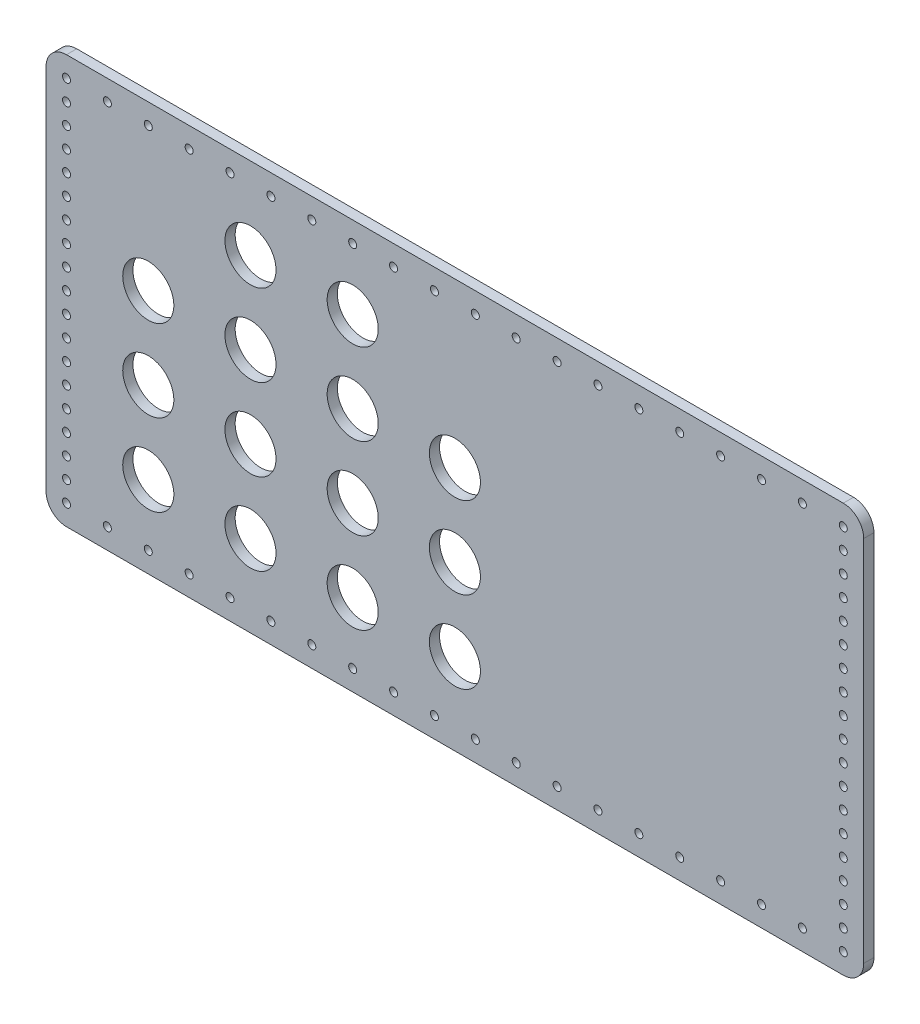
SolidWorks part; units mm, degrees
material "PC High Viscosity"
ref_plane "Front Plane" through (0, 0, 0) normal (0, 0, 1) x (1, 0, 0)
ref_plane "Top Plane" through (0, 0, 0) normal (0, 1, 0) x (1, 0, 0)
ref_plane "Right Plane" through (0, 0, 0) normal (1, 0, 0) x (0, 0, -1)
sketch "Sketch1" plane through (0, 0, 0) normal (0, 0, 1) x (1, 0, 0)
  line L1 (0, 0) -> (508, 0)
  line L2 (0, 0) -> (0, 254)
  line L3 (0, 254) -> (508, 254)
  line L4 (508, 0) -> (508, 254)
  dimension "D1" = 508
  dimension "D2" = 254
extrude "Boss-Extrude1" add sketch "Sketch1" along normal blind 6.35
sketch "Sketch3" plane through (0, 0, 0) normal (0, 0, -1) x (-1, 0, 0)
  line L14 (0, 0) -> (-508, 0) construction
  line L15 (0, 254) -> (0, 0) construction
  line L16 (-127, 152.4) -> (-190.5, 152.4) construction
  line L17 (-127, 152.4) -> (-127, 203.2) construction
  circle A5 centre (-127, 152.4) radius 15.875
  circle A6 centre (-63.5, 152.4) radius 15.875
  circle A7 centre (-190.5, 152.4) radius 15.875
  circle A8 centre (-127, 101.6) radius 15.875
  circle A9 centre (-63.5, 101.6) radius 15.875
  circle A10 centre (-190.5, 101.6) radius 15.875
  circle A11 centre (-127, 50.8) radius 15.875
  circle A12 centre (-63.5, 50.8) radius 15.875
  circle A13 centre (-190.5, 50.8) radius 15.875
  circle A15 centre (-190.5, 152.4) radius 15.875
  circle A16 centre (-254, 152.4) radius 15.875
  circle A17 centre (-254, 101.6) radius 15.875
  circle A18 centre (-254, 50.8) radius 15.875
  circle A19 centre (-190.5, 203.2) radius 15.875 [skipped]
  circle A20 centre (-254, 203.2) radius 15.875 [skipped]
  circle A21 centre (-254, 152.4) radius 15.875 [skipped]
  circle A22 centre (-254, 101.6) radius 15.875 [skipped]
  circle A23 centre (-127, 203.2) radius 15.875
  circle A24 centre (-190.5, 203.2) radius 15.875
  circle A25 centre (-190.5, 152.4) radius 15.875
  circle A26 centre (-190.5, 101.6) radius 15.875
  dimension "D2" = 31.75
  dimension "D3" = 50.8
  dimension "D4" = 50.8
  dimension "D5" = 50.8
  dimension "D6" = 63.5
  dimension "D7" = 63.5
  dimension "D8" = 2
  dimension "D9" = 2
  dimension "D10" = 63.5
  dimension "D11" = 50.8
  dimension "D12" = 63.5
extrude "Cut-Extrude2" cut sketch "Sketch3" against normal through all contours A18 | A17 | A16 | A24 | A7 | A10 | A8 | A5 | A23 | A6 | A9 | A12 | A11 | A13 region at (127, 152.4, 0) region at (63.5, 152.4, 0) region at (190.5, 152.4, 0) region at (127, 101.6, 0) region at (63.5, 101.6, 0) region at (190.5, 101.6, 0) region at (127, 50.8, 0) region at (63.5, 50.8, 0) region at (190.5, 50.8, 0) region at (254, 152.4, 0) region at (254, 101.6, 0) region at (254, 50.8, 0) region at (190.5, 203.2, 0) region at (127, 203.2, 0)
sketch "Sketch4" plane through (0, 0, 0) normal (0, 0, -1) x (-1, 0, 0)
  line L0 (0, 254) -> (0, 0) construction
  line L1 (-508, 254) -> (0, 254) construction
  line L2 (-12.7, 241.3) -> (-38.1, 241.3) construction
  line L3 (-495.3, 241.3) -> (-495.3, 228.6) construction
  line L4 (-495.3, 12.7) -> (-469.9, 12.7) construction
  circle A0 centre (-12.7, 241.3) radius 2.4892
  circle A1 centre (-38.1, 241.3) radius 2.4892
  circle A2 centre (-63.5, 241.3) radius 2.4892
  circle A3 centre (-88.9, 241.3) radius 2.4892
  circle A4 centre (-114.3, 241.3) radius 2.4892
  circle A5 centre (-139.7, 241.3) radius 2.4892
  circle A6 centre (-165.1, 241.3) radius 2.4892
  circle A7 centre (-190.5, 241.3) radius 2.4892
  circle A8 centre (-215.9, 241.3) radius 2.4892
  circle A9 centre (-241.3, 241.3) radius 2.4892
  circle A10 centre (-266.7, 241.3) radius 2.4892
  circle A11 centre (-292.1, 241.3) radius 2.4892
  circle A12 centre (-317.5, 241.3) radius 2.4892
  circle A13 centre (-342.9, 241.3) radius 2.4892
  circle A14 centre (-368.3, 241.3) radius 2.4892
  circle A15 centre (-393.7, 241.3) radius 2.4892
  circle A16 centre (-419.1, 241.3) radius 2.4892
  circle A17 centre (-444.5, 241.3) radius 2.4892
  circle A18 centre (-469.9, 241.3) radius 2.4892
  circle A19 centre (-495.3, 241.3) radius 2.4892
  circle A20 centre (-495.3, 228.6) radius 2.4892
  circle A21 centre (-12.7, 228.6) radius 2.4892
  circle A22 centre (-495.3, 215.9) radius 2.4892
  circle A23 centre (-12.7, 215.9) radius 2.4892
  circle A24 centre (-495.3, 203.2) radius 2.4892
  circle A25 centre (-12.7, 203.2) radius 2.4892
  circle A26 centre (-495.3, 190.5) radius 2.4892
  circle A27 centre (-12.7, 190.5) radius 2.4892
  circle A28 centre (-495.3, 177.8) radius 2.4892
  circle A29 centre (-12.7, 177.8) radius 2.4892
  circle A30 centre (-495.3, 165.1) radius 2.4892
  circle A31 centre (-12.7, 165.1) radius 2.4892
  circle A32 centre (-495.3, 152.4) radius 2.4892
  circle A33 centre (-12.7, 152.4) radius 2.4892
  circle A34 centre (-495.3, 139.7) radius 2.4892
  circle A35 centre (-12.7, 139.7) radius 2.4892
  circle A36 centre (-495.3, 127) radius 2.4892
  circle A37 centre (-12.7, 127) radius 2.4892
  circle A38 centre (-495.3, 114.3) radius 2.4892
  circle A39 centre (-12.7, 114.3) radius 2.4892
  circle A40 centre (-495.3, 101.6) radius 2.4892
  circle A41 centre (-12.7, 101.6) radius 2.4892
  circle A42 centre (-495.3, 88.9) radius 2.4892
  circle A43 centre (-12.7, 88.9) radius 2.4892
  circle A44 centre (-495.3, 76.2) radius 2.4892
  circle A45 centre (-12.7, 76.2) radius 2.4892
  circle A46 centre (-495.3, 63.5) radius 2.4892
  circle A47 centre (-12.7, 63.5) radius 2.4892
  circle A48 centre (-495.3, 50.8) radius 2.4892
  circle A49 centre (-12.7, 50.8) radius 2.4892
  circle A50 centre (-495.3, 38.1) radius 2.4892
  circle A51 centre (-12.7, 38.1) radius 2.4892
  circle A52 centre (-495.3, 25.4) radius 2.4892
  circle A53 centre (-12.7, 25.4) radius 2.4892
  circle A54 centre (-495.3, 12.7) radius 2.4892
  circle A55 centre (-12.7, 12.7) radius 2.4892
  circle A56 centre (-469.9, 12.7) radius 2.4892
  circle A57 centre (-444.5, 12.7) radius 2.4892
  circle A58 centre (-419.1, 12.7) radius 2.4892
  circle A59 centre (-393.7, 12.7) radius 2.4892
  circle A60 centre (-368.3, 12.7) radius 2.4892
  circle A61 centre (-342.9, 12.7) radius 2.4892
  circle A62 centre (-317.5, 12.7) radius 2.4892
  circle A63 centre (-292.1, 12.7) radius 2.4892
  circle A64 centre (-266.7, 12.7) radius 2.4892
  circle A65 centre (-241.3, 12.7) radius 2.4892
  circle A66 centre (-215.9, 12.7) radius 2.4892
  circle A67 centre (-190.5, 12.7) radius 2.4892
  circle A68 centre (-165.1, 12.7) radius 2.4892
  circle A69 centre (-139.7, 12.7) radius 2.4892
  circle A70 centre (-114.3, 12.7) radius 2.4892
  circle A71 centre (-88.9, 12.7) radius 2.4892
  circle A72 centre (-63.5, 12.7) radius 2.4892
  circle A73 centre (-38.1, 12.7) radius 2.4892
  dimension "D1" = 4.9784
  dimension "D2" = 12.7
  dimension "D3" = 12.7
  dimension "D5" = 25.4
  dimension "D7" = 12.7
  dimension "D9" = 25.4
  dimension "D4" = 20
  dimension "D6" = 19
  dimension "D8" = 19
extrude "Cut-Extrude3" cut sketch "Sketch4" against normal through all
fillet "Fillet1" radius 12.7 4 edges at (508, 0, 3.175) (0, 0, 3.175) (0, 254, 3.175) (508, 254, 3.175)
